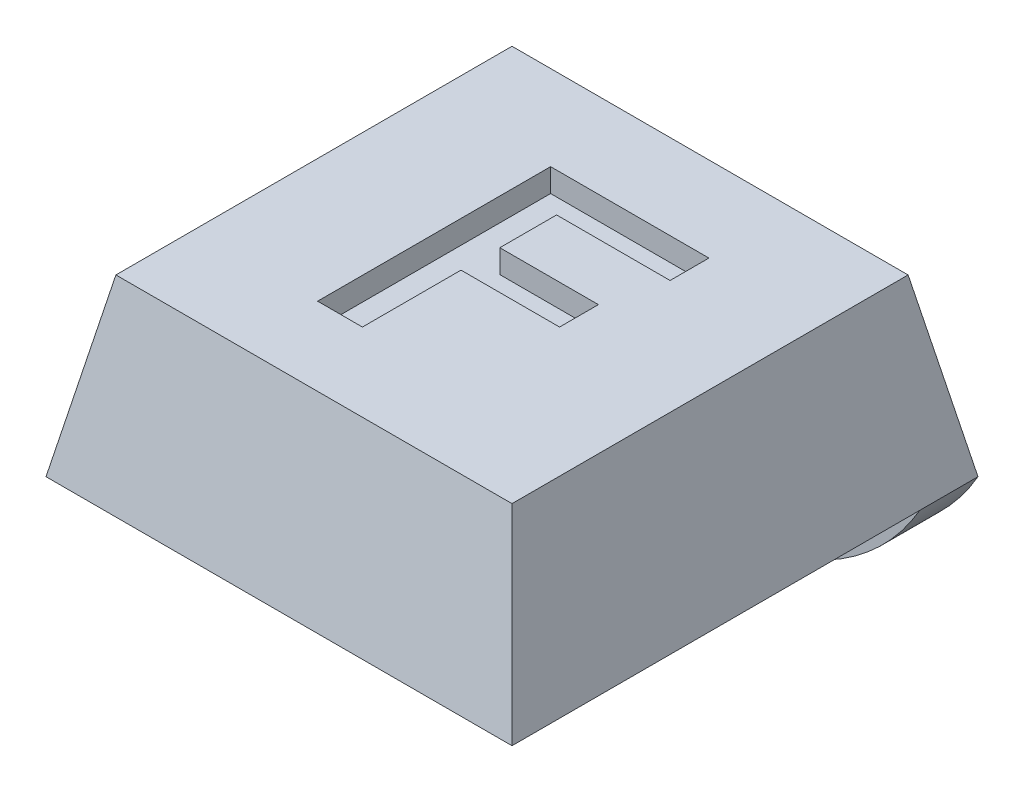
SolidWorks part; units mm, degrees
ref_plane "Front Plane" through (0, 0, 0) normal (0, 0, 1) x (1, 0, 0)
ref_plane "Top Plane" through (0, 0, 0) normal (0, 1, 0) x (1, 0, 0)
ref_plane "Right Plane" through (0, 0, 0) normal (1, 0, 0) x (0, 0, -1)
sketch "Sketch1" plane through (0, 0, 0) normal (0, 1, 0) x (1, 0, 0)
  line L1 (0, 0) -> (8, 0)
  line L2 (0, 0) -> (0, 8)
  line L3 (0, 8) -> (8, 8)
  line L4 (8, 0) -> (8, 8)
  dimension "D1" = 8
  dimension "D2" = 8
extrude "Boss-Extrude1" add sketch "Sketch1" along normal blind 3
sketch "Sketch2" plane through (0, 0, 0) normal (0, 0, 1) x (1, 0, 0)
  line L0 (0, 0) -> (0.6, 3)
  line L1 (0, 3) -> (8, 3) construction
  line L2 (0.6, 3) -> (0, 3)
  line L3 (0, 3) -> (0, 0)
  line L4 (8, 0) -> (7.4, 3)
  line L5 (7.4, 3) -> (8, 3)
  line L6 (8, 3) -> (8, 0)
  dimension "D1" = 0.6
  dimension "D2" = 0.6
extrude "Cut-Extrude1" cut sketch "Sketch2" against normal through all both and the other way through all
sketch "Sketch3" plane through (0, 0, 0) normal (1, 0, 0) x (0, 0, -1)
  line L0 (0, 0) -> (0.6, 3)
  line L1 (8, 3) -> (0, 3) construction
  line L2 (0.6, 3) -> (0, 3)
  line L3 (0, 3) -> (0, 0)
  line L4 (8, 3) -> (7.4, 3)
  line L5 (7.4, 3) -> (8, 0)
  line L6 (8, 3) -> (8, 0)
  dimension "D1" = 0.6
  dimension "D2" = 0.6
extrude "Cut-Extrude2" cut sketch "Sketch3" along normal blind 11
sketch "Sketch4" plane through (0, 0, 0) normal (0, -1, 0) x (1, 0, 0)
  line L0 (8, 0) -> (8, -8) construction
  line L3 (0, 0) -> (8, 0) construction
  circle A0 centre (4, -3.75) radius 1.8
  dimension "D1" = 3.6
  dimension "D2" = 4
  dimension "D3" = 3.75
extrude "Cut-Extrude3" cut sketch "Sketch4" against normal blind 0.8
sketch "Sketch5" plane through (0, 0, 0) normal (0, -1, 0) x (1, 0, 0)
  line L0 (8, 0) -> (8, -8) construction
  line L1 (0, -8) -> (8, -8)
  line L2 (0, -8) -> (0, -7)
  line L3 (0, -7) -> (8, -7)
  line L4 (8, -8) -> (8, -7)
  dimension "D1" = 1
extrude "Boss-Extrude2" add sketch "Sketch5" along normal blind 2
fillet "Fillet1" radius 4 2 edges at (8, -2, -7.5) (0, -2, -7.5)
sketch "Sketch6" plane through (0, 3, 0) normal (0, 1, 0) x (1, 0, 0)
  text T0 "F" font "Arial" height 4
extrude "Cut-Extrude4" cut sketch "Sketch6" against normal blind 0.4
